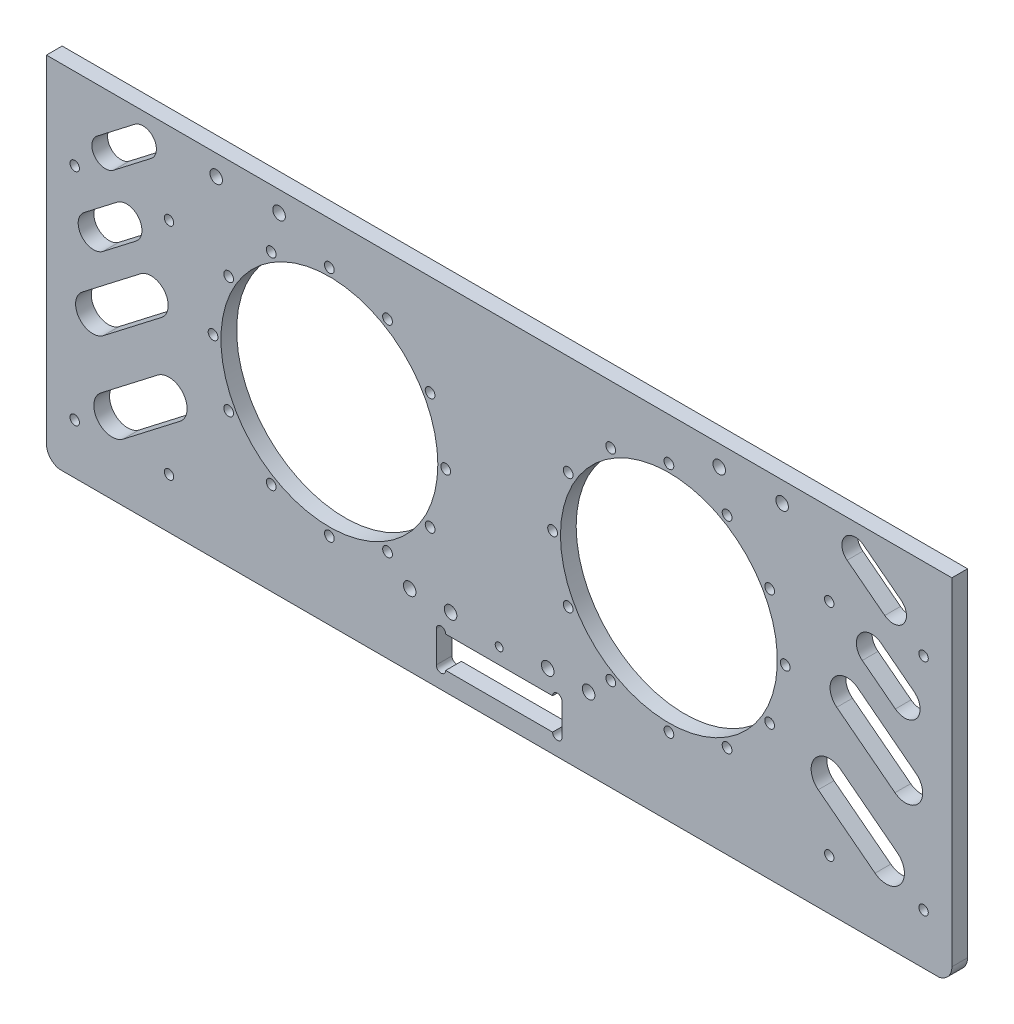
SolidWorks part; units mm, degrees
material "Thornel Mat VMA"
ref_plane "前视基准面" through (0, 0, 0) normal (0, 0, 1) x (1, 0, 0)
ref_plane "上视基准面" through (0, 0, 0) normal (0, 1, 0) x (1, 0, 0)
ref_plane "右视基准面" through (0, 0, 0) normal (1, 0, 0) x (0, 0, -1)
sketch "草图1" plane through (0, 0, 0) normal (0, 0, 1) x (1, 0, 0)
  line L0 (0, 0) -> (0, -50.5) construction
  line L1 (-144, 50.5) -> (144, 50.5)
  line L2 (-144, 50.5) -> (-144, -50.5)
  line L3 (-144, -50.5) -> (144, -50.5)
  line L4 (144, 50.5) -> (144, -50.5)
  line L5 (-144, 50.5) -> (144, -50.5) construction
  line L6 (-144, -50.5) -> (144, 50.5) construction
  line L7 (-54, 0) -> (0, 0) construction
  line L8 (-54, 0) -> (-54, 37) construction
  circle A1 centre (-54, 0) radius 34.5
  circle A2 centre (-54, 37) radius 1.55
  circle A3 centre (-35.5, 32.0429) radius 1.55
  circle A4 centre (-21.9571, 18.5) radius 1.55
  circle A5 centre (-17, 0) radius 1.55
  circle A6 centre (-21.9571, -18.5) radius 1.55
  circle A7 centre (-35.5, -32.0429) radius 1.55
  circle A8 centre (-54, -37) radius 1.55
  circle A9 centre (-72.5, -32.0429) radius 1.55
  circle A10 centre (-86.0429, -18.5) radius 1.55
  circle A11 centre (-91, 0) radius 1.55
  circle A12 centre (-86.0429, 18.5) radius 1.55
  circle A13 centre (-72.5, 32.0429) radius 1.55
  circle A14 centre (72.5, 32.0429) radius 1.55
  circle A15 centre (86.0429, 18.5) radius 1.55
  circle A16 centre (91, 0) radius 1.55
  circle A17 centre (86.0429, -18.5) radius 1.55
  circle A18 centre (72.5, -32.0429) radius 1.55
  circle A19 centre (54, -37) radius 1.55
  circle A20 centre (35.5, -32.0429) radius 1.55
  circle A21 centre (21.9571, -18.5) radius 1.55
  circle A22 centre (17, 0) radius 1.55
  circle A23 centre (21.9571, 18.5) radius 1.55
  circle A24 centre (35.5, 32.0429) radius 1.55
  circle A25 centre (54, 37) radius 1.55
  circle A26 centre (54, 0) radius 34.5
  point P0 (0, 0)
  point P38 (-54, 0)
  dimension "D1" = 288
  dimension "D3" = 108
  dimension "D4" = 69
  dimension "D5" = 37
  dimension "D6" = 3.1
  dimension "D2" = 101
  dimension "D7" = 12
extrude "凸台-拉伸1" add sketch "草图1" along normal mid plane 5
sketch "草图2" plane through (0, 0, 2.5) normal (0, 0, 1) x (1, 0, 0)
  circle A0 centre (135, -45.5) radius 1.5 construction
  circle A1 centre (105, -45.5) radius 1.5 construction
  circle A2 centre (135, 24.5) radius 1.5 construction
  circle A3 centre (105, 24.5) radius 1.5 construction
  circle A4 centre (-105, -45.5) radius 1.5 construction
  circle A5 centre (-135, -45.5) radius 1.5 construction
  circle A6 centre (-105, 24.5) radius 1.5 construction
  circle A7 centre (-135, 24.5) radius 1.5 construction
  circle A8 centre (135, -45.5) radius 1.5
  circle A9 centre (105, -45.5) radius 1.5
  circle A10 centre (135, 24.5) radius 1.5
  circle A11 centre (105, 24.5) radius 1.5
  circle A12 centre (-105, -45.5) radius 1.5
  circle A13 centre (-135, -45.5) radius 1.5
  circle A14 centre (-105, 24.5) radius 1.5
  circle A15 centre (-135, 24.5) radius 1.5
extrude "切除-拉伸1" cut sketch "草图2" against normal blind 5
sketch "草图3" plane through (0, 0, 2.5) normal (0, 0, 1) x (1, 0, 0)
  line L0 (0, 0) -> (0, -50.5) construction
  line L1 (-144, -50.5) -> (144, -50.5) construction
  line L2 (20, -45.5) -> (-20, -45.5)
  line L3 (-20, -45.5) -> (-20, -55.5)
  line L4 (20, -45.5) -> (20, -55.5)
  line L5 (-144, -50.5) -> (-144, -56.5938)
  line L6 (-139.9512, -61.5025) -> (-20.4712, -84.6558)
  line L7 (-19.52, -84.7472) -> (19.5211, -84.7472)
  line L8 (20.4702, -84.6563) -> (139.9491, -61.5577)
  line L9 (144, -56.6486) -> (144, -50.5)
  line L10 (-20, -50.5) -> (20, -50.5)
  line L11 (20, -55.5) -> (-20, -55.5)
  line L12 (-144, -50.5) -> (144, -50.5)
  arc A0 (-17, -45.5) -> (-20, -45.5) centre (-18.5, -45.5) ccw
  arc A1 (17, -45.5) -> (20, -45.5) centre (18.5, -45.5) cw
  arc A2 (17, -55.5) -> (20, -55.5) centre (18.5, -55.5) ccw
  arc A3 (-17, -55.5) -> (-20, -55.5) centre (-18.5, -55.5) cw
  arc A4 (20.4702, -84.6563) -> (19.5211, -84.7472) centre (19.5211, -79.7472) cw
  arc A5 (-19.52, -84.7472) -> (-20.4712, -84.6558) centre (-19.52, -79.7472) cw
  arc A6 (139.9491, -61.5577) -> (144, -56.6486) centre (139, -56.6486) ccw
  arc A7 (-144, -56.5938) -> (-139.9512, -61.5025) centre (-139, -56.5938) ccw
  point P11 (0, -45.5)
  line M39 (-144, -50.5) -> (144, -50.5)
  dimension "D3" = 3
  dimension "D4" = 5
  dimension "D1" = 20
  dimension "D2" = 5
extrude "凸台-拉伸2" add sketch "草图3" against normal blind 5 contours L5 A7 L6 A5 L7 A4 L8 A6 L9 L4 A2 L11 A3 L3 M39 region at (0.0539, -64.0129, 2.5)
extrude "切除-拉伸2" cut sketch "草图3<3>" against normal blind 5 contours L0 L2 L3 M39 | L2 A0 | L2 L0 L12 L4 | A1 L2 region at (10, -48, 2.5) region at (-10, -48, 2.5) region at (18.5, -44.8634, 2.5) region at (-18.5, -44.8634, 2.5)
sketch "草图3<3>" plane through (0, 0, 2.5) normal (0, 0, 1) x (1, 0, 0) same geometry as "草图3"
sketch "草图4" plane through (0, 0, 2.5) normal (0, 0, 1) x (1, 0, 0)
  line L0 (-139.9512, -61.5025) -> (139.9491, -61.5577)
  line L1 (-139.9512, -61.5025) -> (30.7526, -109.9605)
  line L2 (30.7526, -109.9605) -> (139.9491, -61.5577)
extrude "切除-拉伸3" cut sketch "草图4" against normal blind 10
sketch "草图5" plane through (0, 0, 2.5) normal (0, 0, 1) x (1, 0, 0)
  circle A0 centre (28.4533, -38.713) radius 2 construction
  circle A1 centre (-28.4533, -38.713) radius 2 construction
  circle A2 centre (28.4533, -38.713) radius 2
  circle A3 centre (-28.4533, -38.713) radius 2
extrude "切除-拉伸4" cut sketch "草图5" against normal blind 10
sketch "草图6" plane through (0, 0, 2.5) normal (0, 0, 1) x (1, 0, 0)
  circle A0 centre (0, -40.5) radius 1.25 construction
  circle A1 centre (0, -40.5) radius 1.25
extrude "切除-拉伸5" cut sketch "草图6" against normal blind 10
sketch "草图7" plane through (0, 0, 2.5) normal (0, 0, 1) x (1, 0, 0)
  circle A0 centre (90, 44) radius 2 construction
  circle A1 centre (70, 44) radius 2 construction
  circle A2 centre (90, 44) radius 2
  circle A3 centre (70, 44) radius 2
extrude "切除-拉伸6" cut sketch "草图7" against normal blind 5.5
sketch "草图8" plane through (0, 0, 2.5) normal (0, 0, 1) x (1, 0, 0)
  line L6 (-118.5075, 17.3689) -> (-129.0146, 9.2623) construction
  line L7 (-115.5215, 13.4987) -> (-126.0286, 5.3921)
  line L8 (-121.4934, 21.239) -> (-132.0005, 13.1324)
  line L9 (-110.737, 0.8729) -> (-129.2474, -13.4085) construction
  line L10 (-107.3918, -3.4629) -> (-125.9022, -17.7443)
  line L11 (-114.0822, 5.2087) -> (-132.5926, -9.0728)
  line L12 (-105.0459, -24.5358) -> (-123.1185, -38.4794) construction
  line L13 (-101.503, -29.1278) -> (-119.5756, -43.0714)
  line L14 (-108.5887, -19.9438) -> (-126.6614, -33.8874)
  line L15 (-125.2737, 32.8458) -> (-113.3002, 42.0838) construction
  line L16 (-127.8907, 36.2377) -> (-115.9172, 45.4757)
  line L17 (-122.6568, 29.4539) -> (-110.6832, 38.6919)
  line L26 (0, 50.5) -> (0, 0) construction
  line L27 (144, 50.5) -> (-144, 50.5) construction
  line L28 (125.2737, 32.8458) -> (113.3002, 42.0838) construction
  line L29 (127.8907, 36.2377) -> (115.9172, 45.4757)
  line L30 (122.6568, 29.4539) -> (110.6832, 38.6919)
  line L31 (105.0459, -24.5358) -> (123.1185, -38.4794) construction
  line L32 (101.503, -29.1278) -> (119.5756, -43.0714)
  line L33 (108.5887, -19.9438) -> (126.6614, -33.8874)
  line L34 (110.737, 0.8729) -> (129.2474, -13.4085) construction
  line L35 (107.3918, -3.4629) -> (125.9022, -17.7443)
  line L36 (114.0822, 5.2087) -> (132.5926, -9.0728)
  line L37 (118.5075, 17.3689) -> (129.0146, 9.2623) construction
  line L38 (115.5215, 13.4987) -> (126.0286, 5.3921)
  line L39 (121.4934, 21.239) -> (132.0005, 13.1324)
  line L42 (139.9491, -61.5577) -> (-139.9512, -61.5025) construction
  circle A0 centre (-54, 0) radius 42
  circle A1 centre (54, 0) radius 42
  arc A2 (-115.5215, 13.4987) -> (-121.4934, 21.239) centre (-118.5075, 17.3689) ccw
  arc A3 (-132.0005, 13.1324) -> (-126.0286, 5.3921) centre (-129.0146, 9.2623) ccw
  arc A4 (-107.3918, -3.4629) -> (-114.0822, 5.2087) centre (-110.737, 0.8729) ccw
  arc A5 (-132.5926, -9.0728) -> (-125.9022, -17.7443) centre (-129.2474, -13.4085) ccw
  arc A6 (-101.503, -29.1278) -> (-108.5887, -19.9438) centre (-105.0459, -24.5358) ccw
  arc A7 (-126.6614, -33.8874) -> (-119.5756, -43.0714) centre (-123.1185, -38.4794) ccw
  arc A8 (-127.8907, 36.2377) -> (-122.6568, 29.4539) centre (-125.2737, 32.8458) ccw
  arc A9 (-110.6832, 38.6919) -> (-115.9172, 45.4757) centre (-113.3002, 42.0838) ccw
  arc A18 (127.8907, 36.2377) -> (122.6568, 29.4539) centre (125.2737, 32.8458) cw
  arc A19 (110.6832, 38.6919) -> (115.9172, 45.4757) centre (113.3002, 42.0838) cw
  arc A20 (101.503, -29.1278) -> (108.5887, -19.9438) centre (105.0459, -24.5358) cw
  arc A21 (126.6614, -33.8874) -> (119.5756, -43.0714) centre (123.1185, -38.4794) cw
  arc A22 (107.3918, -3.4629) -> (114.0822, 5.2087) centre (110.737, 0.8729) cw
  arc A23 (132.5926, -9.0728) -> (125.9022, -17.7443) centre (129.2474, -13.4085) cw
  arc A24 (115.5215, 13.4987) -> (121.4934, 21.239) centre (118.5075, 17.3689) cw
  arc A25 (132.0005, 13.1324) -> (126.0286, 5.3921) centre (129.0146, 9.2623) cw
  point P8 (-123.761, 13.3156)
  point P13 (-119.9922, -6.2678)
  point P20 (-114.0822, -31.5076)
  point P29 (-119.287, 37.4648)
  point P36 (119.287, 37.4648)
  point P47 (114.0822, -31.5076)
  point P54 (119.9922, -6.2678)
  point P61 (123.761, 13.3156)
  point P65 (1.1926, 0.2746)
  dimension "D1" = 84
  dimension "D2" = 30
extrude "切除-拉伸7" cut sketch "草图8" against normal blind 10 contours L17 A9 L16 A8 | L8 A3 L7 A2 | L11 A5 L10 A4 | L14 A7 L13 A6 | A19 L30 A18 L29 | A25 L39 A24 L38 | A23 L36 A22 L35 | A21 L33 A20 L32 region at (-123.761, 13.3156, 2.5) region at (-119.9922, -6.2678, 2.5) region at (-114.0822, -31.5076, 2.5) region at (-119.287, 37.4648, 2.5) region at (119.287, 37.4648, 2.5) region at (114.0822, -31.5076, 2.5) region at (119.9922, -6.2678, 2.5) region at (123.761, 13.3156, 2.5)
sketch "草图9" plane through (0, 0, 2.5) normal (0, 0, 1) x (1, 0, 0)
  circle A0 centre (15.4533, -38.713) radius 2 construction
  circle A1 centre (-15.4533, -38.713) radius 2 construction
  circle A2 centre (15.4533, -38.713) radius 2
  circle A3 centre (-15.4533, -38.713) radius 2
extrude "切除-拉伸8" cut sketch "草图9" against normal blind 10
sketch "草图10" plane through (0, 0, 2.5) normal (0, 0, 1) x (1, 0, 0)
  line L0 (0, 71.2781) -> (0, -80.7841) construction
  circle A0 centre (90, 44) radius 2 construction
  circle A1 centre (70, 44) radius 2 construction
  circle A2 centre (90, 44) radius 2 construction
  circle A3 centre (70, 44) radius 2 construction
  circle A4 centre (-70, 44) radius 2
  circle A5 centre (-90, 44) radius 2
extrude "切除-拉伸9" cut sketch "草图10" against normal blind 10
